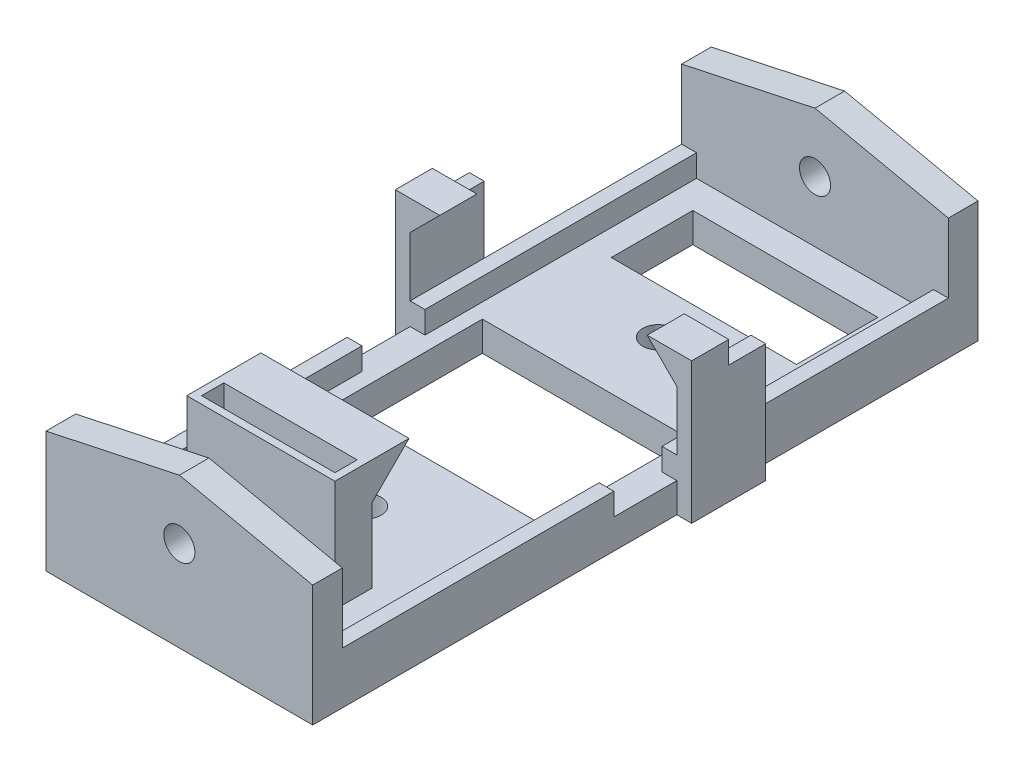
SolidWorks part; units mm, degrees
ref_plane "Front Plane" through (0, 0, 0) normal (0, 0, 1) x (1, 0, 0)
ref_plane "Top Plane" through (0, 0, 0) normal (0, 1, 0) x (1, 0, 0)
ref_plane "Right Plane" through (0, 0, 0) normal (1, 0, 0) x (0, 0, -1)
sketch "Sketch1" plane through (0, 0, 0) normal (0, 0, 1) x (1, 0, 0)
  line L2 (-40.4, 110) -> (0, 118.6383) construction
  line L3 (-18, 114.7896) -> (0, 114.7896)
  line L4 (0, 114.7896) -> (18, 114.7896)
  line L5 (0, 118.6383) -> (40.4, 110) construction
  line L11 (18, 114.7896) -> (18, 121.7896)
  line L12 (18, 121.7896) -> (16, 121.7896)
  line L13 (16, 121.7896) -> (16, 118.7896)
  line L14 (16, 118.7896) -> (-16, 118.7896)
  line L15 (-16, 118.7896) -> (-16, 121.7896)
  line L16 (-16, 121.7896) -> (-18, 121.7896)
  line L17 (-18, 121.7896) -> (-18, 114.7896)
  point P15 (0, 118.7896)
  dimension "D1" = 32
  dimension "D2" = 2
  dimension "D3" = 3
  dimension "D4" = 4
extrude "Boss-Extrude1" add sketch "Sketch1" along normal up to surface (89.8 mm away)
sketch "Sketch2" plane through (0, 114.7896, 0) normal (0, -1, 0) x (1, 0, 0)
  line L0 (18, 89.8) -> (18, 0) construction
  line L5 (-14, 54.9) -> (14, 54.9)
  line L6 (-14, 54.9) -> (-14, 34.9)
  line L7 (-14, 34.9) -> (14, 34.9)
  line L8 (14, 54.9) -> (14, 34.9)
  point P4 (0, 34.9)
  point P8 (18, 44.9)
  point P9 (14, 44.9)
  dimension "D1" = 4
  dimension "D2" = 20
extrude "Cut-Extrude1" cut sketch "Sketch2" against normal up to next
sketch "Sketch3" plane through (-18, 0, 0) normal (-1, 0, 0) x (0, 0, 1)
  line L0 (89.8, 121.7896) -> (0, 121.7896) construction
  line L1 (40.65, 118.7896) -> (49.15, 118.7896)
  line L2 (40.65, 118.7896) -> (40.65, 121.7896)
  line L3 (40.65, 121.7896) -> (49.15, 121.7896)
  line L4 (49.15, 118.7896) -> (49.15, 121.7896)
  line L5 (89.8, 118.7896) -> (0, 118.7896) construction
  point P9 (44.9, 121.7896)
  point P10 (44.9, 121.7896)
  dimension "D1" = 8.5
extrude "Cut-Extrude2" cut sketch "Sketch3" against normal through all
sketch "Sketch4" plane through (0, 118.7896, 0) normal (0, 1, 0) x (1, 0, 0)
  circle A0 centre (0, -25.15) radius 2.1 construction
  circle A1 centre (0, -64.65) radius 2.1 construction
  circle A2 centre (0, -25.15) radius 2.1
  circle A3 centre (0, -64.65) radius 2.1
extrude "Cut-Extrude3" cut sketch "Sketch4" against normal through all
ref_plane "Plane2" through (0, 0, 44.9) normal (0, 0, -1) x (-1, 0, 0)
sketch "Sketch5" plane through (0, 0, 0) normal (0, 0, 1) x (1, 0, 0)
  line L0 (-18, 114.7896) -> (-18, 131.1512)
  line L1 (-56.4, 122.9405) -> (0, 135) construction
  line L2 (-18, 131.1512) -> (0, 135)
  line L3 (0, 135) -> (18, 131.1512)
  line L4 (0, 135) -> (56.4, 122.9405) construction
  line L5 (18, 131.1512) -> (18, 114.7896)
  line L6 (18, 114.7896) -> (-18, 114.7896)
  line L7 (0.6273, 134.8659) -> (54.0273, 123.4479) construction
  line L8 (-54.0273, 123.4479) -> (-0.6273, 134.8659) construction
  circle A0 centre (0, 127) radius 2.1
  dimension "D1" = 4.2
  dimension "D2" = 8
extrude "Boss-Extrude2" add sketch "Sketch5" along normal blind 4
mirror "Mirror1" about plane through (0, 0, 44.9) normal (0, 0, -1) of "Boss-Extrude2"
sketch "Sketch6" plane through (0, 118.7896, 0) normal (0, 1, 0) x (1, 0, 0)
  line L1 (12.5, -19) -> (-12.5, -19)
  line L2 (12.5, -19) -> (12.5, -8)
  line L3 (12.5, -8) -> (-12.5, -8)
  line L4 (-12.5, -19) -> (-12.5, -8)
  point P4 (0, -8)
  dimension "D1" = 11
  dimension "D2" = 25
  dimension "D3" = 8
extrude "Cut-Extrude4" cut sketch "Sketch6" against normal through all
sketch "Sketch8" plane through (0, 118.7896, 0) normal (0, 1, 0) x (1, 0, 0)
  line L0 (16, -85.8) -> (-16, -85.8) construction
  line L1 (9, -77.8) -> (-9, -77.8)
  line L2 (9, -77.8) -> (9, -74.8)
  line L3 (9, -74.8) -> (-9, -74.8)
  line L4 (-9, -77.8) -> (-9, -74.8)
  line L6 (10, -73.8) -> (-10, -73.8)
  line L7 (-10, -78.8) -> (-10, -73.8)
  line L8 (10, -78.8) -> (-10, -78.8)
  line L9 (10, -78.8) -> (10, -73.8)
  point P6 (0, -85.8)
  point P7 (0, -77.8)
  dimension "D1" = 8
  dimension "D2" = 3
  dimension "D3" = 18
  dimension "D4" = 1
extrude "Boss-Extrude3" add sketch "Sketch8" along normal blind 15
sketch "Sketch9" plane through (-10, 0, 0) normal (-1, 0, 0) x (0, 0, 1)
  line L0 (73.8, 128.7896) -> (68.8, 133.7896)
  line L1 (73.8, 133.7896) -> (73.8, 118.7896) construction
  line L2 (68.8, 133.7896) -> (73.8, 133.7896)
  line L3 (73.8, 133.7896) -> (73.8, 128.7896)
  dimension "D1" = 5
  dimension "D2" = 45
extrude "Boss-Extrude4" add sketch "Sketch9" against normal up to surface (20 mm away) up to face at (10, 126.2896, 76.3)
sketch "Sketch13" plane through (0, 118.7896, 0) normal (0, 1, 0) x (1, 0, 0)
  line L4 (-9, -77.8) -> (9, -77.8)
  line L5 (9, -77.8) -> (9, -74.8)
  line L6 (9, -74.8) -> (-9, -74.8)
  line L7 (-9, -74.8) -> (-9, -77.8)
  line L8 (-9, -77.8) -> (9, -77.8)
  line L9 (9, -77.8) -> (9, -74.8)
  line L10 (9, -74.8) -> (-9, -74.8)
  line L11 (-9, -74.8) -> (-9, -77.8)
  dimension "D1" = 0
extrude "Cut-Extrude5" cut sketch "Sketch13" against normal through all
sketch "Sketch10" plane through (0, 114.7896, 0) normal (0, 1, 0) x (1, 0, 0)
  line L0 (18, -40.65) -> (18, -4) construction
  line L1 (18, -40.65) -> (20, -40.65)
  line L2 (18, -40.65) -> (18, -30.65)
  line L3 (18, -30.65) -> (20, -30.65)
  line L4 (20, -40.65) -> (20, -30.65)
  line L5 (0, -1000) -> (0, 49000) construction
  line L6 (-18, -30.65) -> (-20, -30.65)
  line L7 (-18, -40.65) -> (-18, -30.65)
  line L8 (-18, -40.65) -> (-20, -40.65)
  line L9 (-20, -40.65) -> (-20, -30.65)
  dimension "D1" = 10
  dimension "D2" = 2
extrude "Boss-Extrude5" add sketch "Sketch10" along normal offset from surface (16 mm away) 3
sketch "Sketch12" plane through (0, 0, 40.65) normal (0, 0, 1) x (1, 0, 0)
  line L0 (20, 129.7896) -> (20, 133.7896)
  line L1 (20, 133.7896) -> (14, 133.7896)
  line L2 (14, 133.7896) -> (18, 129.7896)
  line L3 (18, 129.7896) -> (20, 129.7896)
  line L4 (-18, 133.7896) -> (18, 133.7896) construction
  line L5 (18, 114.7896) -> (18, 131.1512) construction
  line L6 (20, 130.7896) -> (20, 114.7896) construction
  line L7 (18, 130.7896) -> (18, 121.7896) construction
  line L8 (0, -868.0678) -> (0, 49131.9322) construction
  line L9 (-18, 129.7896) -> (-20, 129.7896)
  line L10 (-14, 133.7896) -> (-18, 129.7896)
  line L11 (-20, 133.7896) -> (-14, 133.7896)
  line L12 (-20, 129.7896) -> (-20, 133.7896)
  dimension "D1" = 45
  dimension "D2" = 6
extrude "Boss-Extrude6" add sketch "Sketch12" against normal blind 5
equation "\"width\"= 24"
equation "\"thk\"= 3"
equation "\"holesize\"= 4.2"
equation "\"holedistance\"= ( 20 + 12 ) / 2"
equation "\"threaded_hole\"= 3.9"
equation "\"fillet_radius\"= 2"
equation "\"ground_clearance\"= 25"
equation "\"tire_thk\"= 3"
equation "\"innerwheel_diam\" = \"wheel_diam\"-2*\"tire_thk\""
equation "\"innerwheel_thk\"= 8"
equation "\"wheel_diam\"= 2*(\"width\"/2+\"ground_clearance\")"
equation "\"coloursensor_holesize\"= 2.65"
equation "\"hole_to_edge\" = 4"
equation "\"D1@Sketch5\"=\"holesize\""
